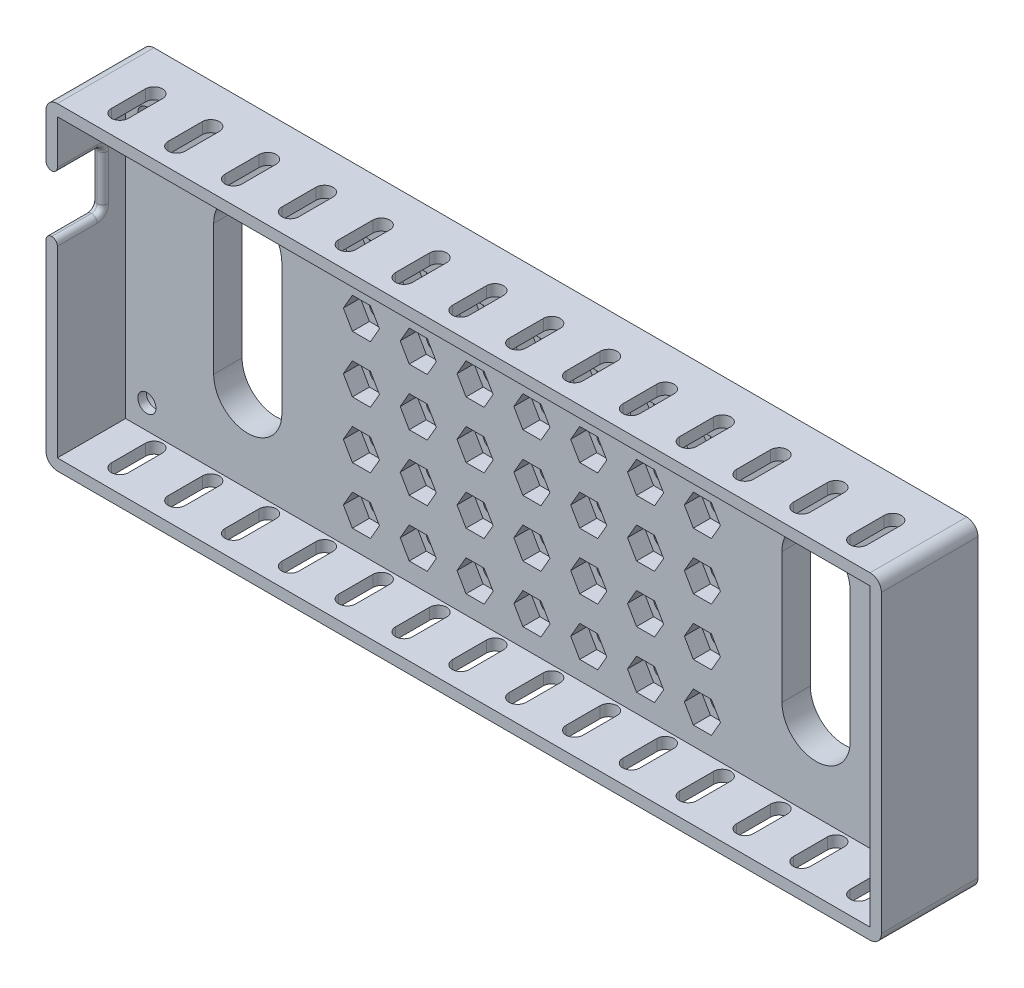
SolidWorks part; units mm, degrees
note: The reader was unsure of these and kept them because the rebuilt part matched: shared geometry of "Sketch2<4>", "Sketch4<3>".
ref_plane "Front Plane" through (0, 0, 0) normal (0, 0, 1) x (1, 0, 0)
ref_plane "Top Plane" through (0, 0, 0) normal (0, 1, 0) x (1, 0, 0)
ref_plane "Right Plane" through (0, 0, 0) normal (1, 0, 0) x (0, 0, -1)
sketch "Sketch2" plane through (0, 0, 0) normal (0, 0, 1) x (1, 0, 0)
  line L0 (-73.5, 28) -> (73.5, 28)
  line L1 (-71.5, 26) -> (71.5, 26)
  line L2 (-71.5, 26) -> (-71.5, -26)
  line L3 (-71.5, -26) -> (71.5, -26)
  line L4 (71.5, 26) -> (71.5, -26)
  line L5 (-71.5, 26) -> (71.5, -26) construction
  line L6 (-71.5, -26) -> (71.5, 26) construction
  line L7 (73.5, 28) -> (73.5, -28)
  line L8 (-73.5, -28) -> (73.5, -28)
  line L9 (-73.5, 28) -> (-73.5, -28)
  point P0 (0, 0)
  dimension "D1" = 143
  dimension "D2" = 52
  dimension "D3" = 2
extrude "Boss-Extrude1" add sketch "Sketch2" along normal blind 5 contours L2 L1 L4 L3
extrude "Boss-Extrude2" add sketch "Sketch2<4>" along normal blind 17
sketch "Sketch2<4>" plane through (0, 0, 0) normal (0, 0, 1) x (1, 0, 0) same geometry as "Sketch2"
sketch "Sketch4" plane through (0, 0, 0) normal (0, 0, -1) x (-1, 0, 0)
  line L1 (-67.75, 21.75) -> (67.75, 21.75) construction
  line L2 (-67.75, 21.75) -> (-67.75, -21.75) construction
  line L3 (-67.75, -21.75) -> (67.75, -21.75) construction
  line L4 (67.75, 21.75) -> (67.75, -21.75) construction
  line L5 (-67.75, 21.75) -> (67.75, -21.75) construction
  line L6 (-67.75, -21.75) -> (67.75, 21.75) construction
  circle A0 centre (-67.75, 21.75) radius 1.6
  circle A1 centre (67.75, 21.75) radius 1.6
  circle A2 centre (67.75, -21.75) radius 1.6
  circle A3 centre (-67.75, -21.75) radius 1.6
  circle A4 centre (-67.75, 21.75) radius 4
  circle A5 centre (67.75, 21.75) radius 4
  circle A6 centre (67.75, -21.75) radius 4
  circle A7 centre (-67.75, -21.75) radius 4
  point P0 (0, 0)
  point P14 (0, 0)
  dimension "D3" = 3.2
  dimension "D4" = 8
  dimension "D1" = 135.5
  dimension "D2" = 43.5
extrude "Cut-Extrude1" cut sketch "Sketch4" against normal blind 16 contours A0 | A3 | A2 | A1
extrude "Cut-Extrude2" cut sketch "Sketch4<3>" against normal blind 3.5
sketch "Sketch4<3>" plane through (0, 0, 0) normal (0, 0, -1) x (-1, 0, 0) same geometry as "Sketch4"
sketch "Sketch5" plane through (0, 0, 0) normal (0, 0, -1) x (-1, 0, 0)
  line L1 (-30, 20) -> (30, 20) construction
  line L2 (-30, 20) -> (-30, -20) construction
  line L3 (-30, -20) -> (30, -20) construction
  line L4 (30, 20) -> (30, -20) construction
  line L5 (-30, 20) -> (30, -20) construction
  line L6 (-30, -20) -> (30, 20) construction
  circle A0 centre (-30, 20) radius 1.6
  point P0 (0, 0)
  dimension "D1" = 60
  dimension "D2" = 40
extrude "Cut-Extrude3" cut sketch "Sketch5" against normal through all
pattern_linear "LPattern1" count 7 spacing 10 along (-1, 0, 0) count 5 spacing 10 along (0, -1, 0) of "Cut-Extrude3"
sketch "Sketch6" plane through (0, 0, 5) normal (0, 0, 1) x (1, 0, 0)
  line L1 (-26.8246, 20) -> (-28.4123, 22.75)
  line L2 (-28.4123, 22.75) -> (-31.5877, 22.75)
  line L3 (-31.5877, 22.75) -> (-33.1754, 20)
  line L4 (-33.1754, 20) -> (-31.5877, 17.25)
  line L5 (-31.5877, 17.25) -> (-28.4123, 17.25)
  line L6 (-28.4123, 17.25) -> (-26.8246, 20)
  line L8 (-71.5, 26) -> (71.5, 26) construction
  circle A0 centre (-30, 20) radius 2.75 construction
  dimension "D1" = 5.5
extrude "Cut-Extrude4" cut sketch "Sketch6" against normal blind 3
pattern_linear "LPattern2" count 7 spacing 10 along (1, 0, 0) count 5 spacing 10 along (0, -1, 0) of "Cut-Extrude4"
sketch "Sketch7" plane through (0, -28, 0) normal (0, -1, 0) x (-1, 0, 0)
  line L0 (64.5, -13) -> (64.5, -7) construction
  line L1 (63, -13) -> (63, -7)
  line L2 (66, -13) -> (66, -7)
  line L3 (73.5, 0) -> (-73.5, 0) construction
  line L4 (73.5, -17) -> (73.5, 0) construction
  arc A0 (63, -13) -> (66, -13) centre (64.5, -13) ccw
  arc A1 (66, -7) -> (63, -7) centre (64.5, -7) ccw
  point P2 (64.5, -10)
  point P11 (0, 0)
  dimension "D1" = 7
  dimension "D3" = 1.5
  dimension "D2" = 9
  dimension "D4" = 6
extrude "Cut-Extrude5" cut sketch "Sketch7" against normal blind 62
pattern_linear "LPattern3" count 14 spacing 10 along (1, 0, 0) of "Cut-Extrude5"
sketch "Sketch9" plane through (-73.5, 0, 0) normal (-1, 0, 0) x (0, 0, 1)
  line L0 (17, 28) -> (0, 28) construction
  line L1 (17, 17.25) -> (9, 17.25)
  line L2 (17, 17.25) -> (17, 7.25)
  line L3 (17, 7.25) -> (9, 7.25)
  line L4 (9, 17.25) -> (9, 7.25)
  line L5 (17, 17.25) -> (9, 7.25) construction
  line L6 (17, 7.25) -> (9, 17.25) construction
  line L7 (17, 28) -> (17, -28) construction
  point P0 (13, 12.25)
  dimension "D2" = 10
  dimension "10.5" = 10.75
  dimension "D3" = 8
extrude "Cut-Extrude6" cut sketch "Sketch9" against normal blind 62
fillet "Fillet1" radius 1 6 edges at (-71.5, 7.25, 13) (-73.5, 7.25, 13) (-73.5, 17.25, 13) (-71.5, 17.25, 13) (-73.5, 12.25, 9) (-71.5, 12.25, 9)
fillet "Fillet2" radius 2 4 edges at (73.5, -28, 8.5) (73.5, 28, 8.5) (-73.5, 28, 8.5) (-73.5, -28, 8.5)
sketch "Sketch10" plane through (0, 0, 0) normal (0, 0, -1) x (-1, 0, 0)
  line L0 (50, -11.5) -> (50, 11.5) construction
  line L1 (44, -11.5) -> (44, 11.5)
  line L2 (56, -11.5) -> (56, 11.5)
  arc A0 (44, -11.5) -> (56, -11.5) centre (50, -11.5) ccw
  arc A1 (56, 11.5) -> (44, 11.5) centre (50, 11.5) ccw
  point P2 (50, 0)
  point P10 (0, 0)
  dimension "D2" = 6
  dimension "D1" = 50
  dimension "D3" = 23
extrude "Cut-Extrude7" cut sketch "Sketch10" against normal blind 62
mirror "Mirror1" about plane through (0, 0, 0) normal (1, 0, 0) of "Cut-Extrude7"
